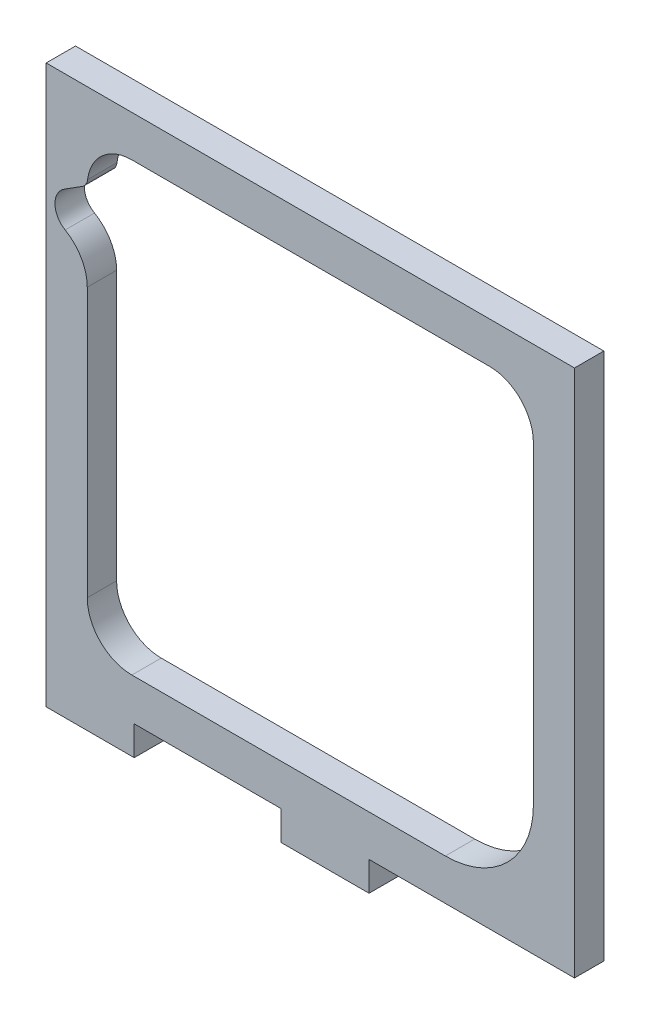
SolidWorks part; units mm, degrees
ref_plane "Front Plane" through (0, 0, 0) normal (0, 0, 1) x (1, 0, 0)
ref_plane "Top Plane" through (0, 0, 0) normal (0, 1, 0) x (1, 0, 0)
ref_plane "Right Plane" through (0, 0, 0) normal (1, 0, 0) x (0, 0, -1)
sketch "Sketch1" plane through (0, 0, 0) normal (0, 0, 1) x (1, 0, 0)
  line L0 (-57.15, -57.15) -> (57.15, -57.15)
  line L1 (-57.15, -57.15) -> (-57.15, 57.15)
  line L2 (-57.15, 57.15) -> (57.15, 57.15)
  line L3 (57.15, -57.15) -> (57.15, 57.15)
  line L4 (-57.15, 31.75) -> (-50.8, 31.75) construction
  line L5 (-57.15, 0) -> (57.15, 0) construction
  line L6 (-50.8, 31.75) -> (-50.8, 57.15) construction
  line L7 (0, 57.15) -> (0, -57.15) construction
  line L8 (-38.608, -48.26) -> (17.088, -48.26)
  line L9 (-48.26, -38.608) -> (-48.26, 4.6862)
  line L10 (48.26, -17.5136) -> (48.26, 38.735)
  line L11 (-48.26, -48.26) -> (59.1365, 59.1365) construction
  line L13 (12.3175, 48.26) -> (38.735, 48.26)
  line L14 (48.26, -17.5136) -> (48.26, -48.26) construction
  line L15 (17.088, -48.26) -> (48.26, -48.26) construction
  line L16 (-48.26, 4.6862) -> (-48.26, 19.5797)
  line L17 (-38.608, 48.26) -> (12.3175, 48.26)
  line L19 (17.088, -48.26) -> (29.21, -48.26)
  line L20 (48.26, -17.5136) -> (48.26, -29.21)
  line L21 (-49.3572, 37.9156) -> (-53.1718, 35.5082)
  arc A9 (-38.608, -48.26) -> (-48.26, -38.608) centre (-38.608, -38.608) cw
  arc A12 (38.735, 48.26) -> (48.26, 38.735) centre (38.735, 38.735) cw
  arc A16 (29.21, -48.26) -> (48.26, -29.21) centre (29.21, -29.21) ccw
  arc A21 (-48.191, 39.7603) -> (-38.608, 48.26) centre (-38.608, 38.608) cw
  arc A22 (-53.1718, 35.5082) -> (-53.0422, 27.9131) centre (-50.8, 31.75) ccw
  arc A23 (-48.26, 19.5797) -> (-53.0422, 27.9131) centre (-57.912, 19.5797) ccw
  arc A24 (-49.3572, 37.9156) -> (-48.191, 39.7603) centre (-50.7128, 40.0636) ccw
  point P0 (0, 0)
  point P1 (0, 0)
  point P16 (0, 0)
  dimension "D4" = 25.4
  dimension "D9" = 8.89
  dimension "D11" = 8.89
  dimension "D12" = 8.89
  dimension "D5" = 6.35
  dimension "D8" = 19.05
  dimension "D10" = 9.525
  dimension "D2" = 9.652
  dimension "D3" = 9.652
  dimension "D13" = 9.652
  dimension "D14" = 2.54
  dimension "D6" = 8.89
  dimension "D7" = 114.3
extrude "Boss-Extrude1" add sketch "Sketch1" along normal mid plane 6.35
sketch "Sketch2" plane through (0, -57.15, 0) normal (0, -1, 0) x (1, 0, 0)
  line L0 (-57.15, -3.175) -> (57.15, -3.175) construction
  line L1 (12.7, 3.175) -> (-6.35, 3.175)
  line L2 (12.7, 3.175) -> (12.7, -3.175)
  line L3 (12.7, -3.175) -> (-6.35, -3.175)
  line L4 (-6.35, 3.175) -> (-6.35, -3.175)
  line L5 (-57.15, 3.175) -> (57.15, 3.175) construction
  line L6 (-38.1, 3.175) -> (-57.15, 3.175)
  line L7 (-38.1, 3.175) -> (-38.1, -3.175)
  line L8 (-38.1, -3.175) -> (-57.15, -3.175)
  line L9 (-57.15, 3.175) -> (-57.15, -3.175)
  line L10 (-57.15, 3.175) -> (-57.15, -3.175) construction
  dimension "D1" = 19.05
  dimension "D2" = 31.75
extrude "Boss-Extrude2" add sketch "Sketch2" along normal blind 6.35
sketch "Sketch3" plane through (0, 0, -3.175) normal (0, 0, -1) x (-1, 0, 0)
  line L0 (57.15, 57.15) -> (57.15, -63.5) construction
  line L1 (57.15, 44.45) -> (63.5, 44.45)
  line L2 (57.15, 44.45) -> (57.15, 19.05)
  line L3 (57.15, 19.05) -> (63.5, 19.05)
  line L4 (63.5, 44.45) -> (63.5, 19.05)
  line L5 (-57.15, 57.15) -> (57.15, 57.15) construction
  point P6 (60.325, 44.45)
  dimension "D1" = 25.4
  dimension "D2" = 6.35
  dimension "D3" = 12.7
extrude "Boss-Extrude3" [suppressed] add sketch "Sketch3" against normal blind 6.35
